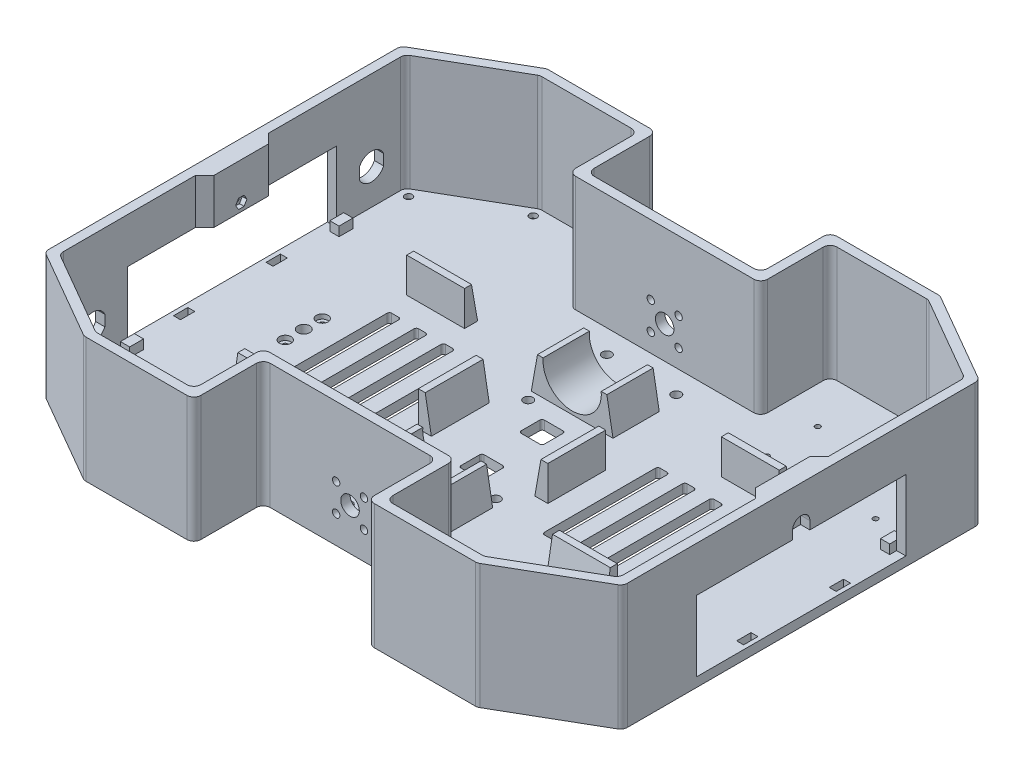
SolidWorks part; units mm, degrees
ref_plane "Front Plane" through (0, 0, 0) normal (0, 0, 1) x (1, 0, 0)
ref_plane "Top Plane" through (0, 0, 0) normal (0, 1, 0) x (1, 0, 0)
ref_plane "Right Plane" through (0, 0, 0) normal (1, 0, 0) x (0, 0, -1)
sketch "Sketch1" plane through (0, 0, 0) normal (0, 1, 0) x (1, 0, 0)
  line L0 (-85, 100) -> (85, 100)
  line L1 (-125, 100) -> (125, 100) construction
  line L2 (-125, 100) -> (-125, -100) construction
  line L3 (-125, -100) -> (125, -100) construction
  line L4 (125, 100) -> (125, -100) construction
  line L5 (85, 100) -> (125, 76.906)
  line L6 (125, 76.906) -> (125, -76.906)
  line L8 (-125, -76.906) -> (-125, 76.906)
  line L9 (-125, 76.906) -> (-85, 100)
  line L10 (-125, 0) -> (125, 0) construction
  line L11 (85, -100) -> (125, -76.906)
  line L12 (-85, -100) -> (85, -100)
  line L13 (-125, -76.906) -> (-85, -100)
  point P4 (0, 100)
  point P6 (-125, 0)
  point P9 (0, 0)
  dimension "D1" = 250
  dimension "D2" = 200
  dimension "D3" = 60
  dimension "D4" = 60
  dimension "D5" = 40
extrude "Boss-Extrude1" add sketch "Sketch1" along normal blind 54
shell "Shell1" thickness 4 removed face at (0, 54, 0)
sketch "Sketch7" plane through (0, 54, 0) normal (0, 1, 0) x (1, 0, 0)
  line L0 (-85, -100) -> (85, -100) construction
  line L1 (-37.5, -70) -> (37.5, -70)
  line L2 (-37.5, -70) -> (-37.5, -100)
  line L3 (-37.5, -100) -> (37.5, -100)
  line L4 (37.5, -70) -> (37.5, -100)
  point P6 (0, -70)
  dimension "D1" = 30
  dimension "D2" = 75
extrude "Cut-Extrude4" cut sketch "Sketch7" against normal up to next
sketch "Sketch8" plane through (0, 4, 0) normal (0, 1, 0) x (1, 0, 0)
  line L0 (-37.5, -96) -> (-37.5, -70)
  line L1 (-37.5, -70) -> (37.5, -70)
  line L2 (37.5, -70) -> (37.5, -96)
  line L3 (-41.5, -96) -> (-41.5, -66)
  line L4 (-41.5, -66) -> (41.5, -66)
  line L5 (41.5, -66) -> (41.5, -96)
  line L6 (-37.5, -96) -> (-41.5, -96)
  line L7 (37.5, -96) -> (41.5, -96)
  dimension "D1" = 4
extrude "Boss-Extrude3" add sketch "Sketch8" along normal up to surface (50 mm away) contours L3 L4 L5 L7 L2 L1 L0 L6 up to face at (0, 54, 19.6)
sketch "Sketch9" plane through (0, 0, 70) normal (0, 0, 1) x (1, 0, 0)
  line B0 (6.0104, 11.9896) -> (-6.0104, 24.0104) construction
  circle B1 centre (0, 18) radius 4
  circle B2 centre (6.0104, 11.9896) radius 1.6
  circle B3 centre (-6.0104, 24.0104) radius 1.6
  circle B4 centre (0, 18) radius 12.5 construction
  line B5 (-6.0104, 11.9896) -> (6.0104, 24.0104) construction
  circle B6 centre (0, 18) radius 4
  circle B7 centre (-6.0104, 11.9896) radius 1.6
  circle B8 centre (6.0104, 24.0104) radius 1.6
  circle B9 centre (0, 18) radius 12.5 construction
  dimension "D1" = 18
sketch_block_instance "Block-JGA25-371-1"
sketch_block "Block1" parameters "D1"=8, "D3"=3.2, "D4"=25, "D2"=17
sketch_block_instance "Block1-1"
extrude "Cut-Extrude5" cut sketch "Sketch9" against normal up to surface (4 mm away) contours B1 | B7 | B3 | B8 | B2 region at (0, 18, 70) region at (6.0104, 11.9896, 70) region at (-6.0104, 24.0104, 70) region at (-6.0104, 11.9896, 70) region at (6.0104, 24.0104, 70) up to face at (0, 29, 66)
sketch "Sketch10" plane through (0, 4, 0) normal (0, 1, 0) x (1, 0, 0)
  line L0 (41.5, -66) -> (-41.5, -66) construction
  line L1 (-15, -26) -> (15, -26)
  line L2 (-15, -26) -> (-15, -46)
  line L3 (-15, -46) -> (15, -46)
  line L4 (15, -26) -> (15, -46)
  point P6 (0, -26)
  dimension "D1" = 30
  dimension "D2" = 20
  dimension "D3" = 20
extrude "Boss-Extrude4" add sketch "Sketch10" along normal blind 15
sketch "Sketch11" plane through (0, 0, 46) normal (0, 0, 1) x (1, 0, 0)
  circle A0 centre (0, 18) radius 12.6
  dimension "D1" = 25.2
extrude "Cut-Extrude6" cut sketch "Sketch11" against normal up to surface (20 mm away) up to face at (0, 11.5, 26)
sketch "Sketch12" plane through (0, 4, 0) normal (0, 1, 0) x (1, 0, 0)
  line L0 (-41.5, -66) -> (41.5, -66) construction
  line L1 (-5, -8) -> (5, -8)
  line L2 (-5, -8) -> (-5, -18)
  line L3 (-5, -18) -> (5, -18)
  line L4 (5, -8) -> (5, -18)
  point P4 (0, -8)
  dimension "D1" = 10
  dimension "D2" = 48
extrude "Cut-Extrude7" cut sketch "Sketch12" against normal through all
fillet "Fillet1" radius 1 4 edges at (-5, 2, 18) (5, 2, 18) (5, 2, 8) (-5, 2, 8)
chamfer "Chamfer1" distance 15 angle 10 2 edges at (-15, 4, 36) (15, 4, 36) first distance on face at (-15, 11.5, 36) first distance on face at (15, 11.5, 36)
sketch "Sketch36" plane through (0, 4, 0) normal (0, 1, 0) x (1, 0, 0)
  line L0 (15, -56) -> (-15, -56) construction
  line L1 (-41.5, -66) -> (41.5, -66) construction
  line L2 (-15, -22) -> (15, -22) construction
  circle A0 centre (15, -56) radius 2
  circle A1 centre (-15, -56) radius 2
  circle A2 centre (-15, -22) radius 2
  circle A3 centre (15, -22) radius 2
  point P4 (0, -56)
  dimension "D1" = 4
  dimension "D2" = 30
  dimension "D3" = 10
  dimension "D4" = 34
extrude "Cut-Extrude22" cut sketch "Sketch36" against normal up to next
mirror "Mirror2" about plane through (0, 0, 0) normal (0, 0, 1) of "Cut-Extrude22", "Fillet1", "Cut-Extrude7", "Cut-Extrude5", "Boss-Extrude3", "Cut-Extrude4", "Cut-Extrude6", "Boss-Extrude4", "Chamfer1"
sketch "Sketch13" plane through (0, 4, 0) normal (0, 1, 0) x (1, 0, 0)
  line L0 (-90, 0) -> (90, 0) construction
  circle A0 centre (-90, 0) radius 2.6
  circle A1 centre (90, 0) radius 2.6
  point P2 (0, 0)
  circle B0 centre (-90.0005, -8) radius 1.1
  circle B1 centre (-89.9995, 8) radius 1.1
  circle B2 centre (89.9995, -8) radius 1.1
  circle B3 centre (90.0005, 8) radius 1.1
  dimension "D2" = 5.2
  dimension "D1" = 180
sketch_block_instance "Ball-Caster-1"
sketch_block "Ball-Caster" parameters "D1"=16, "D2"=2.2, "D3"=16
sketch_block_instance "Ball-Caster-2"
extrude "Cut-Extrude8" cut sketch "Sketch13" against normal blind 10
sketch "Sketch14" plane through (0, 4, 0) normal (0, 1, 0) x (1, 0, 0)
  circle A0 centre (-89.9995, 8) radius 2.5
  circle A1 centre (-90.0005, -8) radius 2.5
  circle A2 centre (90.0005, 8) radius 2.5
  circle A3 centre (89.9995, -8) radius 2.5
  dimension "D1" = 5
extrude "Cut-Extrude9" cut sketch "Sketch14" against normal blind 2
sketch "Sketch16" plane through (-125, 0, 0) normal (-1, 0, 0) x (0, 0, 1)
  line L1 (-45.25, 34.5) -> (45.25, 34.5)
  line L2 (-45.25, 34.5) -> (-45.25, 4)
  line L3 (-45.25, 4) -> (45.25, 4)
  line L4 (45.25, 34.5) -> (45.25, 4)
  line L5 (-76.906, 0) -> (76.906, 0) construction
  point P6 (0, 34.5)
  dimension "D1" = 30.5
  dimension "D2" = 90.5
  dimension "D5" = 4
extrude "Cut-Extrude10" cut sketch "Sketch16" against normal blind 4.2 contours L4 L1 L2 L3 region at (-125, 19.25, 0)
sketch "Sketch19" plane through (0, 4, 0) normal (0, 1, 0) x (1, 0, 0)
  line L0 (-125, 0) -> (0, 0) construction
  line L1 (-123.2, 23.1) -> (-120.2, 23.1)
  line L2 (-123.2, 23.1) -> (-123.2, 16.9)
  line L3 (-123.2, 16.9) -> (-120.2, 16.9)
  line L4 (-120.2, 23.1) -> (-120.2, 16.9)
  line L11 (-125, 45.25) -> (-125, -45.25) construction
  line L12 (-123.2, -16.9) -> (-120.2, -16.9)
  line L13 (-120.2, -23.1) -> (-120.2, -16.9)
  line L14 (-123.2, -23.1) -> (-120.2, -23.1)
  line L15 (-123.2, -23.1) -> (-123.2, -16.9)
  point P6 (-120.2, 20)
  dimension "D1" = 3
  dimension "D2" = 6.2
  dimension "D3" = 1.8
  dimension "D4" = 20
extrude "Cut-Extrude12" cut sketch "Sketch19" against normal up to next
sketch "Sketch26" plane through (-125, 0, 0) normal (-1, 0, 0) x (0, 0, 1)
  line L2 (-45.25, 4) -> (45.25, 4) construction
  line L3 (-76.906, 0) -> (76.906, 0) construction
  line L4 (-45.25, 34.5) -> (45.25, 34.5) construction
  line L5 (-3.75, 38) -> (3.75, 38)
  line L6 (-3.75, 38) -> (-3.75, 34.5)
  line L7 (-3.75, 34.5) -> (3.75, 34.5)
  line L8 (3.75, 38) -> (3.75, 34.5)
  circle A0 centre (0, 38) radius 3.75
  point P5 (0, 0)
  dimension "D1" = 7.5
  dimension "D2" = 34
extrude "Cut-Extrude17" cut sketch "Sketch26" against normal up to next contours L5 A0 | L5 A0 L7 | L6 L5 L8 L7 region at (-125, 39.5915, 0) region at (-125, 36.4504, 0)
sketch "Sketch27" plane through (-121, 0, 0) normal (1, 0, 0) x (0, 0, -1)
  line L0 (74.5966, 54) -> (-74.5966, 54) construction
  line L1 (-9.75, 54) -> (9.75, 54)
  line L2 (-9.75, 54) -> (-9.75, 34.5)
  line L3 (-9.75, 34.5) -> (9.75, 34.5)
  line L4 (9.75, 54) -> (9.75, 34.5)
  line L5 (3.75, 34.5) -> (45.25, 34.5) construction
  point P8 (0, 54)
  point P9 (0, 54)
extrude "Boss-Extrude6" add sketch "Sketch27" along normal blind 4
sketch "Sketch28" plane through (-117, 0, 0) normal (1, 0, 0) x (0, 0, -1)
  line L0 (9.75, 54) -> (-9.75, 54) construction
  line L1 (1.2124, 35.9) -> (2.4249, 38)
  line L2 (2.4249, 38) -> (1.2124, 40.1)
  line L3 (1.2124, 40.1) -> (-1.2124, 40.1)
  line L4 (-1.2124, 40.1) -> (-2.4249, 38)
  line L5 (-2.4249, 38) -> (-1.2124, 35.9)
  line L6 (-1.2124, 35.9) -> (1.2124, 35.9)
  circle A0 centre (0, 38) radius 2.1 construction
  point P11 (0, 54)
  dimension "D1" = 4.2
  dimension "D2" = 34
extrude "Cut-Extrude18" cut sketch "Sketch28" against normal blind 2
sketch "Sketch29" plane through (-121, 0, 0) normal (-1, 0, 0) x (0, 0, 1)
  circle A0 centre (0, 38) radius 1.1
  dimension "D1" = 2.2
extrude "Cut-Extrude19" cut sketch "Sketch29" against normal up to next
sketch "Sketch30" plane through (0, 4, 0) normal (0, 1, 0) x (1, 0, 0)
  line L0 (-125, 0) -> (0, 0) construction
  line L1 (-125, 45.25) -> (-125, -45.25) construction
  line L2 (-121, 74.5966) -> (-121, 45.25) construction
  line L3 (-121, 48.25) -> (-117, 48.25)
  line L4 (-121, 48.25) -> (-121, 42.25)
  line L5 (-121, 42.25) -> (-117, 42.25)
  line L6 (-117, 48.25) -> (-117, 42.25)
  line L7 (-121, -42.25) -> (-117, -42.25)
  line L8 (-117, -48.25) -> (-117, -42.25)
  line L9 (-121, -48.25) -> (-117, -48.25)
  line L10 (-121, -48.25) -> (-121, -42.25)
  point P11 (-121, 45.25)
  dimension "D1" = 4
  dimension "D2" = 6
extrude "Boss-Extrude7" add sketch "Sketch30" along normal blind 4
mirror "Mirror4" about plane through (0, 0, 0) normal (1, 0, 0) of "Cut-Extrude12", "Cut-Extrude10", "Cut-Extrude17", "Cut-Extrude19", "Cut-Extrude18", "Boss-Extrude6", "Boss-Extrude7"
chamfer "Chamfer3" distance 6 angle 45 4 edges at (-121, 44.25, 9.75) (-121, 44.25, -9.75) (121, 44.25, 9.75) (121, 44.25, -9.75)
sketch "Sketch33" plane through (0, 4, 0) normal (0, 1, 0) x (1, 0, 0)
  line L0 (0, 66) -> (0, -66) construction
  line L1 (-108, 35) -> (-28, 35) construction
  line L2 (-108, 35) -> (-108, -35) construction
  line L3 (-108, -35) -> (-28, -35) construction
  line L4 (-28, 35) -> (-28, -35) construction
  line L5 (-111, 38) -> (-25, 38) construction
  line L6 (-25, 38) -> (-25, -38) construction
  line L7 (-111, -38) -> (-25, -38) construction
  line L8 (-111, 38) -> (-111, -38) construction
  line L9 (-121, 74.5966) -> (-121, 15.75) construction
  line L10 (-28, -12.5) -> (-25, -12.5)
  line L11 (-28, -12.5) -> (-28, 12.5)
  line L12 (-28, 12.5) -> (-25, 12.5)
  line L13 (-25, -12.5) -> (-25, 12.5)
  line L14 (-55.5, 38) -> (-80.5, 38)
  line L15 (-55.5, 38) -> (-55.5, 35)
  line L16 (-55.5, 35) -> (-80.5, 35)
  line L17 (-80.5, 38) -> (-80.5, 35)
  line L18 (-80.5, -35) -> (-55.5, -35)
  line L19 (-80.5, -35) -> (-80.5, -38)
  line L20 (-80.5, -38) -> (-55.5, -38)
  line L21 (-55.5, -35) -> (-55.5, -38)
  line L26 (-41.5, 66) -> (41.5, 66) construction
  line L27 (-41.5, -66) -> (41.5, -66) construction
  line L28 (80.5, -38) -> (55.5, -38)
  line L29 (55.5, -35) -> (55.5, -38)
  line L30 (80.5, -35) -> (55.5, -35)
  line L31 (80.5, -35) -> (80.5, -38)
  line L32 (28, 12.5) -> (25, 12.5)
  line L33 (25, -12.5) -> (25, 12.5)
  line L34 (28, -12.5) -> (25, -12.5)
  line L35 (28, -12.5) -> (28, 12.5)
  line L36 (55.5, 35) -> (80.5, 35)
  line L37 (80.5, 38) -> (80.5, 35)
  line L38 (55.5, 38) -> (80.5, 38)
  line L39 (55.5, 38) -> (55.5, 35)
  point P4 (-28, 0)
  point P16 (-28, 0)
  point P21 (-68, 35)
  point P22 (-68, 35)
  point P27 (-68, -35)
  point P28 (-68, -35)
  dimension "D1" = 80
  dimension "D2" = 70
  dimension "D3" = 3
  dimension "D4" = 10
  dimension "D5" = 25
extrude "Boss-Extrude9" add sketch "Sketch33" along normal blind 15
chamfer "Chamfer8" distance 15 angle 10 6 edges at (-68, 4, 38) (-25, 4, 0) (-68, 4, -38) (68, 4, -38) (25, 4, 0) (68, 4, 38) first distance on face at (-68, 11.5, 38) first distance on face at (-25, 11.5, 0) first distance on face at (-68, 11.5, -38) first distance on face at (68, 11.5, -38) first distance on face at (25, 11.5, 0) first distance on face at (68, 11.5, 38)
sketch "Sketch31" plane through (0, 54, 0) normal (0, 1, 0) x (1, 0, 0)
  line L0 (-37.5, 100) -> (-85, 100) construction
  line L1 (-55, 100) -> (55, 100)
  line L2 (-55, 100) -> (-55, -100)
  line L3 (-55, -100) -> (55, -100)
  line L4 (55, 100) -> (55, -100)
  line L5 (37.5, -100) -> (85, -100) construction
  point P8 (0, -100)
  dimension "D1" = 110
extrude "Cut-Extrude20" [suppressed] cut sketch "Sketch31" against normal blind 8
chamfer "Chamfer6" [suppressed] distance 8 angle 45
sketch "Sketch34" plane through (-125, 0, 0) normal (-1, 0, 0) x (0, 0, 1)
  line L0 (55, 21.5952) -> (55, 16.9048)
  line L1 (65.5, 21.5952) -> (65.5, 16.9048)
  line L2 (45.25, 34.5) -> (45.25, 4) construction
  line L3 (-45.25, 34.5) -> (-45.25, 4) construction
  line L4 (0, 54) -> (0, 0) construction
  line L5 (-76.906, 54) -> (76.906, 54) construction
  line L6 (-76.906, 0) -> (76.906, 0) construction
  line L7 (-65.5, 21.5952) -> (-65.5, 16.9048)
  line L8 (-55, 21.5952) -> (-55, 16.9048)
  circle A0 centre (60.25, 19.25) radius 5.75
  circle A1 centre (-60.25, 19.25) radius 5.75
  point P6 (-45.25, 19.25)
  point P7 (45.25, 19.25)
  dimension "D1" = 11.5
  dimension "D2" = 10.5
  dimension "D3" = 15
extrude "Cut-Extrude21" cut sketch "Sketch34" against normal up to next contours A1 L8 L7 | L1 A0 L0 region at (-125, 19.25, 60.25) region at (-125, 19.25, -60.25)
fillet "Fillet2" radius 3 16 edges at (-37.5, 27, 70) (37.5, 27, 70) (37.5, 27, -70) (-37.5, 27, -70) (-37.5, 27, -100) (-85, 27, -100) (-125, 27, -76.906) (-125, 27, 76.906) (-85, 27, 100) (-37.5, 27, 100) (37.5, 27, 100) (85, 27, 100) (125, 27, 76.906) (125, 27, -76.906) (85, 27, -100) (37.5, 27, -100)
fillet "Fillet3" radius 3 16 edges at (121, 29, -74.5966) (83.9282, 29, -96) (41.5, 29, -96) (41.5, 29, -66) (-41.5, 29, -66) (-41.5, 29, -96) (-83.9282, 29, -96) (-121, 29, -74.5966) (-121, 29, 74.5966) (-83.9282, 29, 96) (-41.5, 29, 96) (-41.5, 29, 66) (41.5, 29, 66) (41.5, 29, 96) (83.9282, 29, 96) (121, 29, 74.5966)
sketch "Sketch37" plane through (0, 4, 0) normal (0, 1, 0) x (1, 0, 0)
  line L0 (125, 0) -> (-125, 0) construction
  line L1 (125, -75.1739) -> (125, 75.1739) construction
  line L2 (-125, 75.1739) -> (-125, -75.1739) construction
  line L3 (0, 70) -> (0, -70) construction
  line L4 (34.5, 70) -> (-34.5, 70) construction
  line L5 (34.5, -70) -> (-34.5, -70) construction
  line L6 (84.1962, 100) -> (40.5, 100) construction
  line L7 (123.5, 77.772) -> (85.6962, 99.5981) construction
  circle A0 centre (82.8564, 92) radius 1.6
  circle A1 centre (117, 72.2872) radius 1.6
  circle A4 centre (117, -72.2872) radius 1.6
  circle A5 centre (82.8564, -92) radius 1.6
  circle A6 centre (-82.8564, -92) radius 1.6
  circle A7 centre (-117, -72.2872) radius 1.6
  circle A8 centre (-117, 72.2872) radius 1.6
  circle A9 centre (-82.8564, 92) radius 1.6
  dimension "D5" = 3.2
  dimension "D1" = 8
  dimension "D2" = 8
  dimension "D3" = 8
  dimension "D4" = 8
extrude "Cut-Extrude23" cut sketch "Sketch37" against normal through all
sketch "Sketch38" plane through (0, 4, 0) normal (0, 1, 0) x (1, 0, 0)
  line L1 (-42, 25) -> (-39, 25)
  line L2 (-43, 24) -> (-43, -24)
  line L3 (-42, -25) -> (-39, -25)
  line L4 (-38, 24) -> (-38, -24)
  line L5 (-28, 12.5) -> (-28, -12.5) construction
  line L6 (-54.6667, 24) -> (-54.6667, -24)
  line L7 (-53.6667, 25) -> (-50.6667, 25)
  line L8 (-49.6667, 24) -> (-49.6667, -24)
  line L9 (-53.6667, -25) -> (-50.6667, -25)
  line L10 (-66.3333, 24) -> (-66.3333, -24)
  line L11 (-65.3333, 25) -> (-62.3333, 25)
  line L12 (-61.3333, 24) -> (-61.3333, -24)
  line L13 (-65.3333, -25) -> (-62.3333, -25)
  line L14 (-78, 24) -> (-78, -24)
  line L15 (-77, 25) -> (-74, 25)
  line L16 (-73, 24) -> (-73, -24)
  line L17 (-77, -25) -> (-74, -25)
  line L18 (0, 66) -> (0, -66) construction
  line L19 (-38.5, 66) -> (38.5, 66) construction
  line L20 (-38.5, -66) -> (38.5, -66) construction
  line L22 (77, -25) -> (74, -25)
  line L23 (73, 24) -> (73, -24)
  line L24 (77, 25) -> (74, 25)
  line L25 (78, 24) -> (78, -24)
  line L26 (65.3333, -25) -> (62.3333, -25)
  line L27 (61.3333, 24) -> (61.3333, -24)
  line L28 (65.3333, 25) -> (62.3333, 25)
  line L29 (66.3333, 24) -> (66.3333, -24)
  line L30 (53.6667, -25) -> (50.6667, -25)
  line L31 (49.6667, 24) -> (49.6667, -24)
  line L32 (53.6667, 25) -> (50.6667, 25)
  line L33 (54.6667, 24) -> (54.6667, -24)
  line L34 (38, 24) -> (38, -24)
  line L35 (42, -25) -> (39, -25)
  line L36 (43, 24) -> (43, -24)
  line L37 (42, 25) -> (39, 25)
  arc A0 (-42, 25) -> (-43, 24) centre (-42, 24) ccw
  arc A1 (-39, 25) -> (-38, 24) centre (-39, 24) cw
  arc A2 (-39, -25) -> (-38, -24) centre (-39, -24) ccw
  arc A3 (-43, -24) -> (-42, -25) centre (-42, -24) ccw
  arc A4 (-54.6667, -24) -> (-53.6667, -25) centre (-53.6667, -24) ccw
  arc A5 (-49.6667, -24) -> (-50.6667, -25) centre (-50.6667, -24) cw
  arc A6 (-50.6667, 25) -> (-49.6667, 24) centre (-50.6667, 24) cw
  arc A7 (-54.6667, 24) -> (-53.6667, 25) centre (-53.6667, 24) cw
  arc A8 (-66.3333, 24) -> (-65.3333, 25) centre (-65.3333, 24) cw
  arc A9 (-62.3333, 25) -> (-61.3333, 24) centre (-62.3333, 24) cw
  arc A10 (-61.3333, -24) -> (-62.3333, -25) centre (-62.3333, -24) cw
  arc A11 (-66.3333, -24) -> (-65.3333, -25) centre (-65.3333, -24) ccw
  arc A12 (-78, -24) -> (-77, -25) centre (-77, -24) ccw
  arc A13 (-73, -24) -> (-74, -25) centre (-74, -24) cw
  arc A14 (-78, 24) -> (-77, 25) centre (-77, 24) cw
  arc A15 (-74, 25) -> (-73, 24) centre (-74, 24) cw
  arc A16 (74, 25) -> (73, 24) centre (74, 24) ccw
  arc A17 (78, 24) -> (77, 25) centre (77, 24) ccw
  arc A18 (73, -24) -> (74, -25) centre (74, -24) ccw
  arc A19 (78, -24) -> (77, -25) centre (77, -24) cw
  arc A20 (66.3333, -24) -> (65.3333, -25) centre (65.3333, -24) cw
  arc A21 (61.3333, -24) -> (62.3333, -25) centre (62.3333, -24) ccw
  arc A22 (62.3333, 25) -> (61.3333, 24) centre (62.3333, 24) ccw
  arc A23 (66.3333, 24) -> (65.3333, 25) centre (65.3333, 24) ccw
  arc A24 (54.6667, 24) -> (53.6667, 25) centre (53.6667, 24) ccw
  arc A25 (50.6667, 25) -> (49.6667, 24) centre (50.6667, 24) ccw
  arc A26 (49.6667, -24) -> (50.6667, -25) centre (50.6667, -24) ccw
  arc A27 (54.6667, -24) -> (53.6667, -25) centre (53.6667, -24) cw
  arc A28 (43, -24) -> (42, -25) centre (42, -24) cw
  arc A29 (39, -25) -> (38, -24) centre (39, -24) cw
  arc A30 (39, 25) -> (38, 24) centre (39, 24) ccw
  arc A31 (42, 25) -> (43, 24) centre (42, 24) cw
  point P4 (-38, 0)
  point P22 (-43, 25)
  point P25 (-38, 25)
  point P30 (-43, -25)
  point P109 (43, -25)
  point P110 (38, 25)
  point P111 (43, 25)
  dimension "D5" = 1
  dimension "D1" = 5
  dimension "D2" = 50
  dimension "D3" = 10
  dimension "D4" = 4
extrude "Cut-Extrude24" cut sketch "Sketch38" against normal through all
sketch "Sketch39" plane through (0, 0, 0) normal (0, -1, 0) x (1, 0, 0)
  circle A0 centre (-117, 72.2872) radius 3
  circle A1 centre (-82.8564, 92) radius 3
  circle A2 centre (82.8564, 92) radius 3
  circle A3 centre (117, 72.2872) radius 3
  circle A4 centre (117, -72.2872) radius 3
  circle A5 centre (82.8564, -92) radius 3
  circle A6 centre (-82.8564, -92) radius 3
  circle A7 centre (-117, -72.2872) radius 3
  dimension "D1" = 6
extrude "Cut-Extrude25" cut sketch "Sketch39" against normal blind 2
sketch "Sketch40" plane through (0, 4, 0) normal (0, 1, 0) x (1, 0, 0)
  line L0 (55.5, -63.6449) -> (106.5, -63.6449) construction
  line L1 (55.5, -50.6449) -> (106.5, -50.6449) construction
  line L2 (55.5, -50.6449) -> (55.5, -76.6449) construction
  line L3 (55.5, -76.6449) -> (106.5, -76.6449) construction
  line L4 (106.5, -50.6449) -> (106.5, -76.6449) construction
  line L5 (81, -50.6449) -> (81, -76.6449) construction
  line L6 (55.5, -35) -> (55.5, -40.6449) construction
  line L7 (80.5, -40.6449) -> (55.5, -40.6449) construction
  line L8 (125, 0) -> (-125, 0) construction
  line L9 (125, -75.1739) -> (125, 75.1739) construction
  line L10 (-125, 75.1739) -> (-125, -75.1739) construction
  circle A0 centre (57.5, -52.6449) radius 1.1
  circle A1 centre (104.5, -52.6449) radius 1.1
  circle A2 centre (57.5, -74.6449) radius 1.1
  circle A3 centre (104.5, -74.6449) radius 1.1
  circle A4 centre (104.5, 74.6449) radius 1.1
  circle A5 centre (57.5, 74.6449) radius 1.1
  circle A6 centre (57.5, 52.6449) radius 1.1
  circle A7 centre (104.5, 52.6449) radius 1.1
  dimension "D5" = 2.2
  dimension "D1" = 51
  dimension "D2" = 26
  dimension "D3" = 2
  dimension "D4" = 2
  dimension "D6" = 10
extrude "Cut-Extrude26" cut sketch "Sketch40" against normal blind 10
